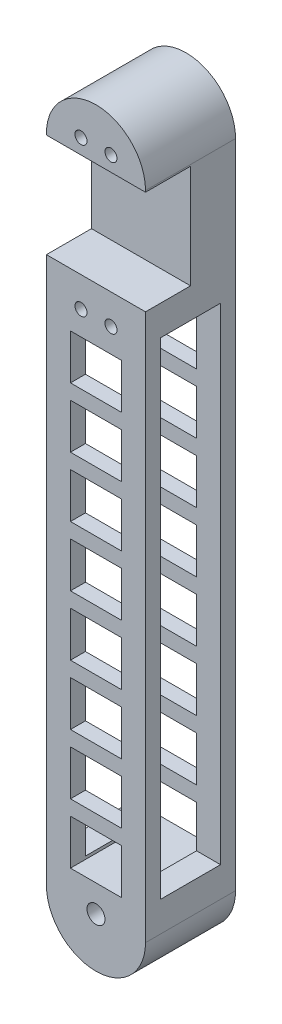
SolidWorks part; units mm, degrees
ref_plane "Front Plane" through (0, 0, 0) normal (0, 0, 1) x (1, 0, 0)
ref_plane "Top Plane" through (0, 0, 0) normal (0, 1, 0) x (1, 0, 0)
ref_plane "Right Plane" through (0, 0, 0) normal (1, 0, 0) x (0, 0, -1)
sketch "Sketch1" plane through (0, 0, 0) normal (0, 0, 1) x (1, 0, 0)
  line L0 (0, -41.8852) -> (0, 175.1148) construction
  line L1 (-16.5, -41.8852) -> (-16.5, 175.1148)
  line L2 (16.5, -41.8852) -> (16.5, 175.1148)
  arc A0 (-16.5, -41.8852) -> (16.5, -41.8852) centre (0, -41.8852) ccw
  arc A1 (16.5, 175.1148) -> (-16.5, 175.1148) centre (0, 175.1148) ccw
  circle A2 centre (0, 165.1148) radius 4
  circle A3 centre (5, 179.6148) radius 2
  circle A4 centre (-5, 179.6148) radius 2
  circle A5 centre (5, 130.1148) radius 2
  circle A6 centre (-5, 130.1148) radius 2
  circle A7 centre (0, -41.8852) radius 3
  circle A8 centre (0, 165.1148) radius 9.5
  point P3 (0, 66.6148)
  point P21 (0, 155.6148)
  dimension "D1" = 217
  dimension "D3" = 8
  dimension "D13" = 6
  dimension "D14" = 19
  dimension "D15" = 4
  dimension "D16" = 4
  dimension "D17" = 4
  dimension "D18" = 4
  dimension "D2" = 33
  dimension "D4" = 14.5
  dimension "D5" = 14.5
  dimension "D6" = 10
  dimension "D7" = 5
  dimension "D8" = 5
  dimension "D9" = 5
  dimension "D10" = 35
  dimension "D11" = 35
  dimension "D12" = 5
extrude "Boss-Extrude2" add sketch "Sketch1" along normal blind 30 contours L0 A2 | A2 L0 | L0 A8 A2 | L2 A1 L1 A0 A7 A8 A6 A5 A4 A3 | A8 L0 A2 region at (-4.5349, 165.1148, 0) region at (4.5349, 165.1148, 0) region at (-1.6977, 165.1148, 0) region at (1.6977, 165.1148, 0) region at (-13.9783, 66.6148, 0)
extrude "Cut-Extrude1" cut sketch "Sketch1<4>" along normal blind 39 contours L0 A2 | A2 L0 region at (-1.6977, 165.1148, 0) region at (1.6977, 165.1148, 0)
sketch "Sketch1<4>" plane through (0, 0, 0) normal (0, 0, 1) x (1, 0, 0) same geometry as "Sketch1"
extrude "Cut-Extrude2" cut sketch "Sketch1<5>" along normal blind 6 contours A8 L0 A2 | L0 A8 A2 region at (-4.5349, 165.1148, 0) region at (4.5349, 165.1148, 0)
sketch "Sketch1<5>" plane through (0, 0, 0) normal (0, 0, 1) x (1, 0, 0) same geometry as "Sketch1"
sketch "Sketch3" plane through (0, 0, 30) normal (0, 0, 1) x (1, 0, 0)
  line L1 (-19.1196, 140.1148) -> (19.5723, 140.1148)
  line L2 (-19.1196, 140.1148) -> (-19.1196, 174.6148)
  line L3 (-19.1196, 174.6148) -> (19.5723, 174.6148)
  line L4 (19.5723, 140.1148) -> (19.5723, 174.6148)
  line L5 (-19.1196, 140.1148) -> (19.5723, 174.6148) construction
  line L6 (-19.1196, 174.6148) -> (19.5723, 140.1148) construction
  circle A0 centre (-5, 179.6148) radius 2 construction
  circle A1 centre (5, 130.1148) radius 2 construction
  point P0 (0.2264, 157.3648)
  point P5 (0.2264, 174.6148)
  dimension "D1" = 5
  dimension "D2" = 10
extrude "Cut-Extrude5" cut sketch "Sketch3" against normal blind 15 contours L2 L1 L4 L3
sketch "Sketch4" plane through (0, 0, 30) normal (0, 0, 1) x (1, 0, 0)
  line L0 (-16.5, -41.8852) -> (-16.5, 140.1148) construction
  line L1 (-8.5, 107.1148) -> (8.5, 107.1148)
  line L2 (-8.5, 107.1148) -> (-8.5, 122.1148)
  line L3 (-8.5, 122.1148) -> (8.5, 122.1148)
  line L4 (8.5, 107.1148) -> (8.5, 122.1148)
  line L5 (-8.5, 107.1148) -> (8.5, 122.1148) construction
  line L6 (-8.5, 122.1148) -> (8.5, 107.1148) construction
  line L7 (16.5, -41.8852) -> (16.5, 140.1148) construction
  line L9 (-8.5, 87.1148) -> (8.5, 87.1148)
  line L10 (-8.5, 87.1148) -> (-8.5, 102.1148)
  line L11 (-8.5, 102.1148) -> (8.5, 102.1148)
  line L12 (8.5, 87.1148) -> (8.5, 102.1148)
  line L13 (-8.5, 87.1148) -> (8.5, 102.1148) construction
  line L14 (-8.5, 102.1148) -> (8.5, 87.1148) construction
  line L15 (-8.5, 67.1148) -> (8.5, 67.1148)
  line L16 (-8.5, 67.1148) -> (-8.5, 82.1148)
  line L17 (-8.5, 82.1148) -> (8.5, 82.1148)
  line L18 (8.5, 67.1148) -> (8.5, 82.1148)
  line L19 (-8.5, 67.1148) -> (8.5, 82.1148) construction
  line L20 (-8.5, 82.1148) -> (8.5, 67.1148) construction
  line L21 (-8.5, 47.1148) -> (8.5, 47.1148)
  line L22 (-8.5, 47.1148) -> (-8.5, 62.1148)
  line L23 (-8.5, 62.1148) -> (8.5, 62.1148)
  line L24 (8.5, 47.1148) -> (8.5, 62.1148)
  line L25 (-8.5, 47.1148) -> (8.5, 62.1148) construction
  line L26 (-8.5, 62.1148) -> (8.5, 47.1148) construction
  line L27 (-8.5, 27.1148) -> (8.5, 27.1148)
  line L28 (-8.5, 27.1148) -> (-8.5, 42.1148)
  line L29 (-8.5, 42.1148) -> (8.5, 42.1148)
  line L30 (8.5, 27.1148) -> (8.5, 42.1148)
  line L31 (-8.5, 27.1148) -> (8.5, 42.1148) construction
  line L32 (-8.5, 42.1148) -> (8.5, 27.1148) construction
  line L33 (-8.5, 7.1148) -> (8.5, 7.1148)
  line L34 (-8.5, 7.1148) -> (-8.5, 22.1148)
  line L35 (-8.5, 22.1148) -> (8.5, 22.1148)
  line L36 (8.5, 7.1148) -> (8.5, 22.1148)
  line L37 (-8.5, 7.1148) -> (8.5, 22.1148) construction
  line L38 (-8.5, 22.1148) -> (8.5, 7.1148) construction
  line L39 (-8.5, -12.8852) -> (8.5, -12.8852)
  line L40 (-8.5, -12.8852) -> (-8.5, 2.1148)
  line L41 (-8.5, 2.1148) -> (8.5, 2.1148)
  line L42 (8.5, -12.8852) -> (8.5, 2.1148)
  line L43 (-8.5, -12.8852) -> (8.5, 2.1148) construction
  line L44 (-8.5, 2.1148) -> (8.5, -12.8852) construction
  line L45 (-8.5, -32.8852) -> (8.5, -32.8852)
  line L46 (-8.5, -32.8852) -> (-8.5, -17.8852)
  line L47 (-8.5, -17.8852) -> (8.5, -17.8852)
  line L48 (8.5, -32.8852) -> (8.5, -17.8852)
  line L49 (-8.5, -32.8852) -> (8.5, -17.8852) construction
  line L50 (-8.5, -17.8852) -> (8.5, -32.8852) construction
  circle A0 centre (-5, 130.1148) radius 2 construction
  point P0 (0, 114.6148)
  point P11 (0, 94.6148)
  point P16 (0, 74.6148)
  point P21 (0, 54.6148)
  point P26 (0, 34.6148)
  point P31 (0, 14.6148)
  point P36 (0, -5.3852)
  point P41 (0, -25.3852)
  dimension "D1" = 8
  dimension "D2" = 15
  dimension "D3" = 17
  dimension "D4" = 8
  dimension "D5" = 8
  dimension "D6" = 15
  dimension "D7" = 17
  dimension "D8" = 5
  dimension "D9" = 5
  dimension "D10" = 15
  dimension "D11" = 17
  dimension "D12" = 15
  dimension "D13" = 5
  dimension "D14" = 17
  dimension "D15" = 15
  dimension "D16" = 5
  dimension "D17" = 17
  dimension "D18" = 15
  dimension "D19" = 5
  dimension "D20" = 17
  dimension "D21" = 15
  dimension "D22" = 5
  dimension "D23" = 17
  dimension "D24" = 15
  dimension "D25" = 5
  dimension "D26" = 17
extrude "Cut-Extrude6" cut sketch "Sketch4" against normal blind 33 contours L2 L1 L4 L3 | L10 L9 L12 L11 | L16 L15 L18 L17 | L22 L21 L24 L23 | L28 L27 L30 L29 | L34 L33 L36 L35 | L40 L39 L42 L41 | L46 L45 L48 L47
sketch "Sketch6" plane through (16.5, 0, 0) normal (1, 0, 0) x (0, 0, -1)
  line L0 (-15, 140.1148) -> (-30, 140.1148) construction
  line L1 (-25, -31.8852) -> (-5, -31.8852)
  line L2 (-25, -31.8852) -> (-25, 130.1148)
  line L3 (-25, 130.1148) -> (-5, 130.1148)
  line L4 (-5, -31.8852) -> (-5, 130.1148)
  line L5 (-25, -31.8852) -> (-5, 130.1148) construction
  line L6 (-25, 130.1148) -> (-5, -31.8852) construction
  line L7 (-30, -41.8852) -> (0, -41.8852) construction
  line L8 (0, -41.8852) -> (0, 175.1148) construction
  line L9 (-30, -41.8852) -> (-30, 140.1148) construction
  point P0 (-15, 49.1148)
  dimension "D1" = 10
  dimension "D2" = 10
  dimension "D3" = 5
  dimension "D4" = 5
extrude "Cut-Extrude7" cut sketch "Sketch6" against normal blind 33 contours L1 L4 L3 L2 | L2 L1 L4 L3 region at (16.5, 49.1148, 15)
